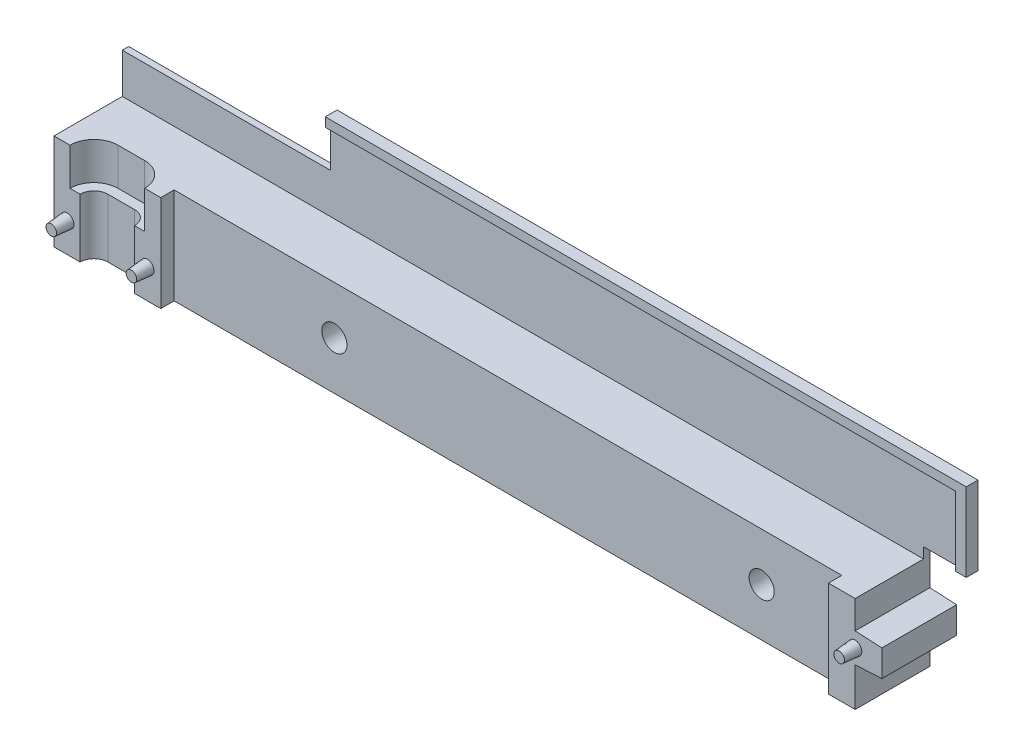
SolidWorks part; units mm, degrees
ref_plane "Front Plane" through (0, 0, 0) normal (0, 0, 1) x (1, 0, 0)
ref_plane "Top Plane" through (0, 0, 0) normal (0, 1, 0) x (1, 0, 0)
ref_plane "Right Plane" through (0, 0, 0) normal (1, 0, 0) x (0, 0, -1)
ref_axis "X-Axis" through (0, 0, 0) along (1, 0, 0)
ref_axis "Y-Axis" through (0, 42.2917, 0) along (0, -1, 0)
ref_axis "Z-Axis" through (0, 0, 55.0015) along (0, 0, -1)
sketch "Sketch1" plane through (0, 0, 0) normal (0, 0, 1) x (1, 0, 0)
  line L1 (-127.8191, -9.8629) -> (22.1809, -9.8629)
  line L2 (22.1809, -9.8629) -> (22.1809, -2.6129)
  line L3 (22.1809, -2.6129) -> (27.1809, -2.6129)
  line L4 (27.1809, -2.6129) -> (27.1809, 2.8871)
  line L5 (27.1809, 2.8871) -> (22.1809, 2.8871)
  line L6 (22.1809, 2.8871) -> (22.1809, 10.1371)
  line L7 (22.1809, 10.1371) -> (31.1809, 10.1371)
  line L8 (31.1809, 10.1371) -> (31.1809, 23.6371)
  line L10 (-127.8191, 15.6371) -> (-127.8191, -9.8629)
  line L12 (-88.8191, -25.8695) -> (-88.8191, 48.9262) construction
  line L13 (31.1809, 13.1371) -> (10.3885, 13.1371) construction
  line L14 (31.1809, 23.6371) -> (-88.8191, 23.6371) construction
  line L15 (-88.8191, 23.6371) -> (-88.8191, 15.6371)
  line L16 (-88.8191, 15.6371) -> (-127.8191, 15.6371)
  line L17 (31.1809, 23.6371) -> (31.1809, 24.8371)
  line L18 (31.1809, 24.8371) -> (-88.8191, 24.8371)
  line L19 (-88.8191, 24.8371) -> (-88.8191, 23.6371)
  point P5 (27.1809, 0.1371)
  dimension "D2" = 10
  dimension "D3" = 20
  dimension "D4" = 5.5
  dimension "D5" = 9
  dimension "D7" = 120
  dimension "D8" = 5
  dimension "D10" = 3
  dimension "D11" = 8
  dimension "D12" = 10.5
  dimension "D13" = 1.2
  dimension "D14" = 150
extrude "Boss-Extrude1" add sketch "Sketch1" along normal blind 14 and the other way blind 14
sketch "Sketch2" plane through (-127.8191, 0, 0) normal (-1, 0, 0) x (0, 0, 1)
  line L0 (-14, -9.8629) -> (14, -9.8629) construction
  line L1 (-12.8, 23.1371) -> (12.8, 23.1371) construction
  line L2 (-12.8, 23.1371) -> (-12.8, 8.1371)
  line L3 (-12.8, 8.1371) -> (12.8, 8.1371)
  line L4 (12.8, 23.1371) -> (12.8, 8.1371)
  line L5 (-14, 24.8371) -> (-14, 15.6371) construction
  line L7 (-14, 2.8871) -> (14, 2.8871) construction
  line L8 (-14, 15.6371) -> (-14, -9.8629) construction
  line L9 (14, 15.6371) -> (14, -9.8629) construction
  line L10 (0, 2.8871) -> (0, 23.1371) construction
  line L11 (-12.8, 23.1371) -> (-11.8, 23.1371)
  line L12 (-11.8, 23.1371) -> (-11.8, 24.8371)
  line L13 (-14, 24.8371) -> (14, 24.8371) construction
  line L14 (-11.8, 24.8371) -> (11.8, 24.8371)
  line L15 (11.8, 24.8371) -> (11.8, 23.1371)
  line L16 (11.8, 23.1371) -> (12.8, 23.1371)
  point P6 (0, 23.1371)
  dimension "D1" = 33
  dimension "D2" = 18
  dimension "D3" = 1
  dimension "D4" = 1
  dimension "D5" = 15
  dimension "D7" = 1.2
extrude "Cut-Extrude1" cut sketch "Sketch2" against normal offset from surface (157 mm away) 2 up to face at (31.1809, 17.4871, 0)
sketch "Sketch8" plane through (0, 0, 0) normal (0, 0, 1) x (1, 0, 0)
  line L0 (-127.8191, 15.6371) -> (-127.8191, -9.8629) construction
  line L1 (-107.8191, 24.8371) -> (17.1809, 24.8371)
  line L2 (-107.8191, 24.8371) -> (-107.8191, -9.8629)
  line L3 (-107.8191, -9.8629) -> (17.1809, -9.8629)
  line L4 (17.1809, 24.8371) -> (17.1809, -9.8629)
  line L5 (-127.8191, -9.8629) -> (22.1809, -9.8629) construction
  line L7 (22.1809, 2.8871) -> (22.1809, 10.1371) construction
  line L8 (29.1809, 24.8371) -> (-88.8191, 24.8371) construction
  point P12 (22.1809, 6.5121)
  dimension "D1" = 20
  dimension "D2" = 5
extrude "Cut-Extrude4" cut sketch "Sketch8" against normal blind 2.5 and the other way blind 2.5 contours L2 L3 L4 L1
sketch "Sketch9" plane through (0, 0, 0) normal (0, 0, 1) x (1, 0, 0)
  line L0 (-107.8191, -0.8629) -> (17.1809, -0.8629) construction
  line L1 (-107.8191, 8.1371) -> (-107.8191, -9.8629) construction
  line L2 (17.1809, 8.1371) -> (17.1809, -9.8629) construction
  circle A0 centre (-77.8191, -0.8629) radius 2.35
  circle A1 centre (2.1809, -0.8629) radius 2.35
  dimension "D1" = 4.7
  dimension "D2" = 80
  dimension "D3" = 15
extrude "Cut-Extrude5" cut sketch "Sketch9" against normal through all and the other way through all
chamfer "Chamfer2" distance 5 angle 3 2 edges at (27.1809, -2.6129, 0) (27.1809, 2.8871, 0) first distance on face at (24.6809, -2.6129, 0) first distance on face at (24.6809, 2.8871, 0)
sketch "Sketch14" plane through (0, 8.1371, 0) normal (0, 1, 0) x (1, 0, 0)
  line L0 (-120.3191, 4.5) -> (-115.3191, 4.5)
  line L1 (-115.3191, -4.5) -> (-120.3191, -4.5)
  line L2 (-107.8191, 0) -> (-127.8191, 0) construction
  line L3 (-107.8191, 2.5) -> (-107.8191, -2.5) construction
  line L5 (-127.8191, 12.8) -> (-127.8191, -12.8) construction
  arc A0 (-115.3191, 4.5) -> (-115.3191, -4.5) centre (-115.3191, 0) cw
  arc A1 (-120.3191, -4.5) -> (-120.3191, 4.5) centre (-120.3191, 0) cw
  point P16 (-117.8191, 0)
  dimension "D1" = 4.5
  dimension "D2" = 5
  dimension "D3" = 2.5
extrude "Cut-Extrude8" cut sketch "Sketch14" against normal blind 7
sketch "Sketch15" plane through (0, 1.1371, 0) normal (0, 1, 0) x (1, 0, 0)
  line L7 (-120.3191, -2.6) -> (-115.3191, -2.6)
  line L8 (-115.3191, 2.6) -> (-120.3191, 2.6)
  arc A2 (-120.3191, 4.5) -> (-120.3191, -4.5) centre (-120.3191, 0) ccw construction
  arc A3 (-115.3191, -4.5) -> (-115.3191, 4.5) centre (-115.3191, 0) ccw construction
  arc A6 (-120.3191, 2.6) -> (-120.3191, -2.6) centre (-120.3191, 0) ccw
  arc A7 (-115.3191, -2.6) -> (-115.3191, 2.6) centre (-115.3191, 0) ccw
  dimension "D2" = 2.6
extrude "Cut-Extrude9" cut sketch "Sketch15" against normal through all
sketch "Sketch16" plane through (0, 0, 0) normal (0, 0, 1) x (1, 0, 0)
  line L1 (-137.4451, 59.0989) -> (76.8996, 59.0989)
  line L2 (-137.4451, 59.0989) -> (-137.4451, -25.5467)
  line L3 (-137.4451, -25.5467) -> (76.8996, -25.5467)
  line L4 (76.8996, 59.0989) -> (76.8996, -25.5467)
extrude "Cut-Extrude10" cut sketch "Sketch16" along normal through all
sketch "Sketch17" plane through (0, 0, 0) normal (0, 0, 1) x (1, 0, 0)
  line L1 (31.1809, 24.8371) -> (29.1809, 24.8371)
  line L2 (31.1809, 24.8371) -> (31.1809, 10.1371)
  line L3 (31.1809, 10.1371) -> (29.1809, 10.1371)
  line L4 (29.1809, 24.8371) -> (29.1809, 10.1371)
extrude "Cut-Extrude11" cut sketch "Sketch17" against normal up to surface (11.8 mm away) up to face at (-29.8191, 23.9871, -11.8)
sketch "Sketch19" plane through (0, 0, 0) normal (0, 0, 1) x (1, 0, 0)
  line L0 (17.1809, 0.1371) -> (27.1809, 0.1371) construction
  line L1 (27.1809, 2.6251) -> (27.1809, -2.3509) construction
  line L3 (-125.3191, -4.3629) -> (-110.3191, -4.3629) construction
  line L5 (-117.8191, -9.8629) -> (-117.8191, 1.1371) construction
  line L8 (17.1809, 8.1371) -> (17.1809, -9.8629) construction
  line L11 (-115.3191, -9.8629) -> (-120.3191, -9.8629) construction
  line L12 (-115.3191, 1.1371) -> (-120.3191, 1.1371) construction
  circle A0 centre (-125.3191, -4.3629) radius 1.25
  circle A1 centre (-110.3191, -4.3629) radius 1.25
  circle A2 centre (22.1809, 0.1371) radius 1.25
  point P17 (-117.8191, -4.3629)
  dimension "D2" = 2.5
  dimension "D1" = 15
extrude "Boss-Extrude5" add sketch "Sketch19" along normal blind 3 separate body
chamfer "Chamfer3" distance 3 angle 5 1 edges at (23.4309, 0.1371, 3) first distance on face at (23.4309, 0.1371, 3)
chamfer "Chamfer4" distance 3 angle 5 1 edges at (-109.0691, -4.3629, 3) first distance on face at (-109.0691, -4.3629, 3)
chamfer "Chamfer5" distance 3 angle 5 1 edges at (-124.0691, -4.3629, 3) first distance on face at (-124.0691, -4.3629, 3)
equation "\"Largeur Bande\"= 24.3"
equation "\"Largeur Feeder\"= \"Largeur Rail\" + 1.2 + 1.2 + 0.3"
equation "\"Largeur Rail\"= \"Largeur Bande\" + 1"
equation "\"D1@Boss-Extrude1\"=\"Largeur Feeder\"/2"
equation "\"D2@Boss-Extrude1\"=\"Largeur Feeder\"/2"
